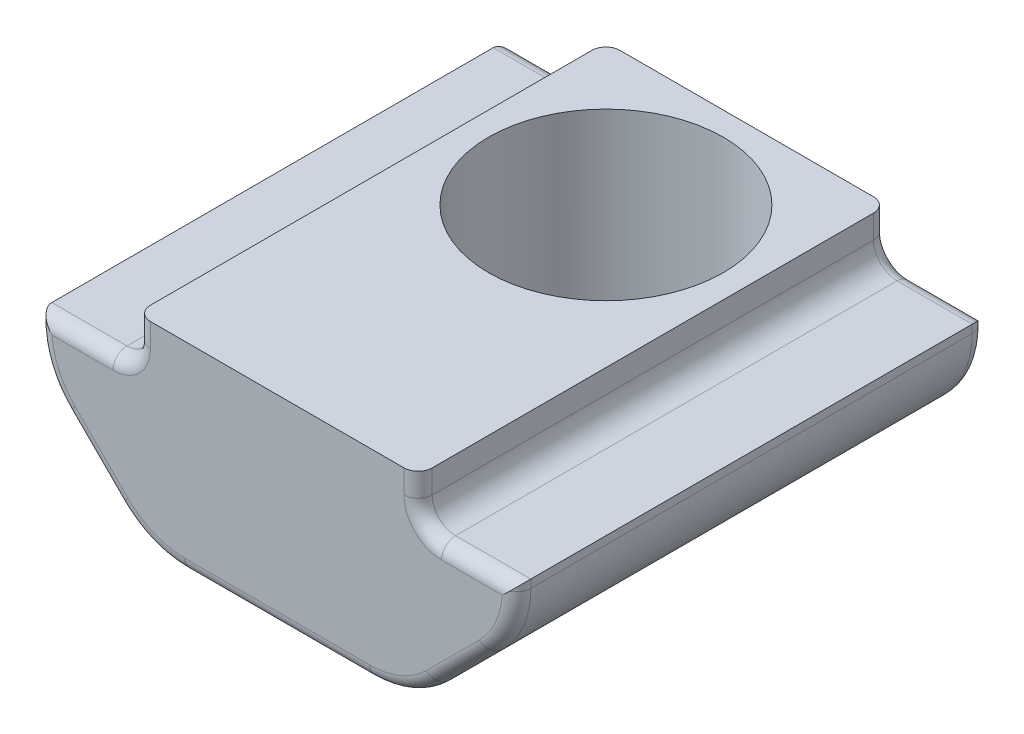
SolidWorks part; units mm, degrees
material "不锈钢 (铁素体)"
ref_plane "前视基准面" through (0, 0, 0) normal (0, 0, 1) x (1, 0, 0)
ref_plane "上视基准面" through (0, 0, 0) normal (0, 1, 0) x (1, 0, 0)
ref_plane "右视基准面" through (0, 0, 0) normal (1, 0, 0) x (0, 0, -1)
sketch "草图1" plane through (0, 0, 0) normal (0, 0, 1) x (1, 0, 0)
  line L0 (0, 0) -> (0, 8533.2886) construction
  line L1 (-3, 4.3) -> (3, 4.3)
  line L2 (3, 4.3) -> (3, 3.8)
  line L3 (3.5, 3.3) -> (5.1, 3.3)
  line L4 (5.1, 3.3) -> (5.1, 3.1284)
  line L5 (4.5142, 1.7142) -> (3.3858, 0.5858)
  line L6 (1.9716, 0) -> (-1.9716, 0)
  line L7 (-4.5142, 1.7142) -> (-3.3858, 0.5858)
  line L8 (-5.1, 3.3) -> (-5.1, 3.1284)
  line L9 (-3.5, 3.3) -> (-5.1, 3.3)
  line L10 (-3, 4.3) -> (-3, 3.8)
  arc A0 (-5.1, 3.1284) -> (-4.5142, 1.7142) centre (-3.1, 3.1284) ccw
  arc A1 (5.1, 3.1284) -> (4.5142, 1.7142) centre (3.1, 3.1284) cw
  arc A2 (1.9716, 0) -> (3.3858, 0.5858) centre (1.9716, 2) ccw
  arc A3 (-3.3858, 0.5858) -> (-1.9716, 0) centre (-1.9716, 2) ccw
  arc A4 (-3.5, 3.3) -> (-3, 3.8) centre (-3.5, 3.8) ccw
  arc A5 (3.5, 3.3) -> (3, 3.8) centre (3.5, 3.8) cw
  point P11 (0, 0)
  point P15 (0, 4.3)
  point P17 (-5.1, 2.3)
  point P20 (5.1, 2.3)
  point P23 (2.8, 0)
  point P26 (-2.8, 0)
  point P29 (-3, 3.3)
  point P32 (3, 3.3)
  dimension "D7" = 2
  dimension "D8" = 0.5
  dimension "D1" = 3.3
  dimension "D2" = 10.2
  dimension "D3" = 4.3
  dimension "D4" = 45
  dimension "D5" = 1
  dimension "D6" = 6
extrude "凸台-拉伸1" add sketch "草图1" along normal blind 10
fillet "圆角3" radius 0.3 30 edges at (-5.1, 3.2142, 10) (-3, 4.05, 10) (3, 4.05, 0) (5.1, 3.2142, 0) (3.95, 1.15, 10) (2.7369, 0.1522, 10) (0, 0, 10) (-2.7369, 0.1522, 10) (-3.95, 1.15, 10) (-4.9478, 2.3631, 10) (-4.3, 3.3, 10) (-3.1464, 3.4464, 10) (4.3, 3.3, 0) (3.1464, 3.4464, 0) (-3.95, 1.15, 0) (-2.7369, 0.1522, 0) (0, 0, 0) (2.7369, 0.1522, 0) (3.95, 1.15, 0) (4.9478, 2.3631, 0) (5.1, 3.2142, 10) (4.9478, 2.3631, 10) (-5.1, 3.2142, 0) (-4.9478, 2.3631, 0) (3, 4.05, 10) (3.1464, 3.4464, 10) (-3, 4.05, 0) (-3.1464, 3.4464, 0) (4.3, 3.3, 10) (-4.3, 3.3, 0)
sketch "草图2" plane through (0, 4.3, 0) normal (0, 1, 0) x (1, 0, 0)
  circle A0 centre (0, -3) radius 2.5
  dimension "D1" = 5
  dimension "D2" = 3
extrude "切除-拉伸1" cut sketch "草图2" against normal blind 6
